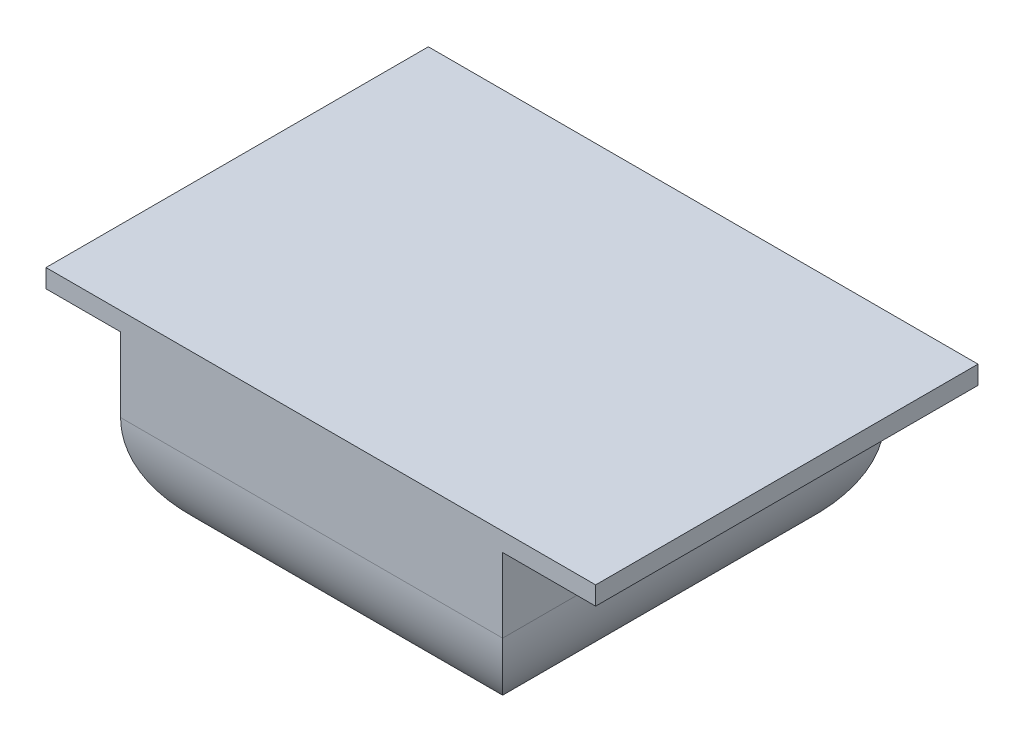
SolidWorks part; units mm, degrees
ref_plane "Front Plane" through (0, 0, 0) normal (0, 0, 1) x (1, 0, 0)
ref_plane "Top Plane" through (0, 0, 0) normal (0, 1, 0) x (1, 0, 0)
ref_plane "Right Plane" through (0, 0, 0) normal (1, 0, 0) x (0, 0, -1)
sketch "Sketch1" plane through (0, 0, 0) normal (0, 0, 1) x (1, 0, 0)
  line L1 (-22, 11) -> (24, 11)
  line L2 (-22, 11) -> (-22, -11.4681)
  line L3 (-22, -11.4681) -> (24, -11.4681)
  line L4 (24, 11) -> (24, -11.4681)
  dimension "D1" = 11
  dimension "D2" = 24
extrude "Boss-Extrude1" add sketch "Sketch1" along normal blind 32
sketch "Sketch2" plane through (0, 0, 0) normal (0, 0, 1) x (1, 0, 0)
  line L0 (-22, 9.457) -> (-15.7548, 9.457)
  line L1 (-22, 11) -> (-22, -11.4681) construction
  line L2 (-15.7548, 9.457) -> (-15.7548, -6.7526)
  line L3 (-15.7548, -6.7526) -> (16.2182, -6.7526)
  line L4 (16.2182, -6.7526) -> (16.2182, 9.457)
  line L5 (16.2182, 9.457) -> (24, 9.457)
  line L6 (24, -11.4681) -> (24, 11) construction
  line L7 (24, 9.457) -> (24, 11)
  line L8 (24, 11) -> (-22, 11) construction
  line L9 (24, 11) -> (-22, 11)
  line L10 (-22, 11) -> (-22, 9.457)
extrude "Cut-Extrude3" cut sketch "Sketch2" along normal through all flip side to cut
fillet "Fillet1" radius 10 4 edges at (0.2317, -6.7526, 0) (0.2317, -6.7526, 32) (16.2182, -6.7526, 16) (-15.7548, -6.7526, 16)
